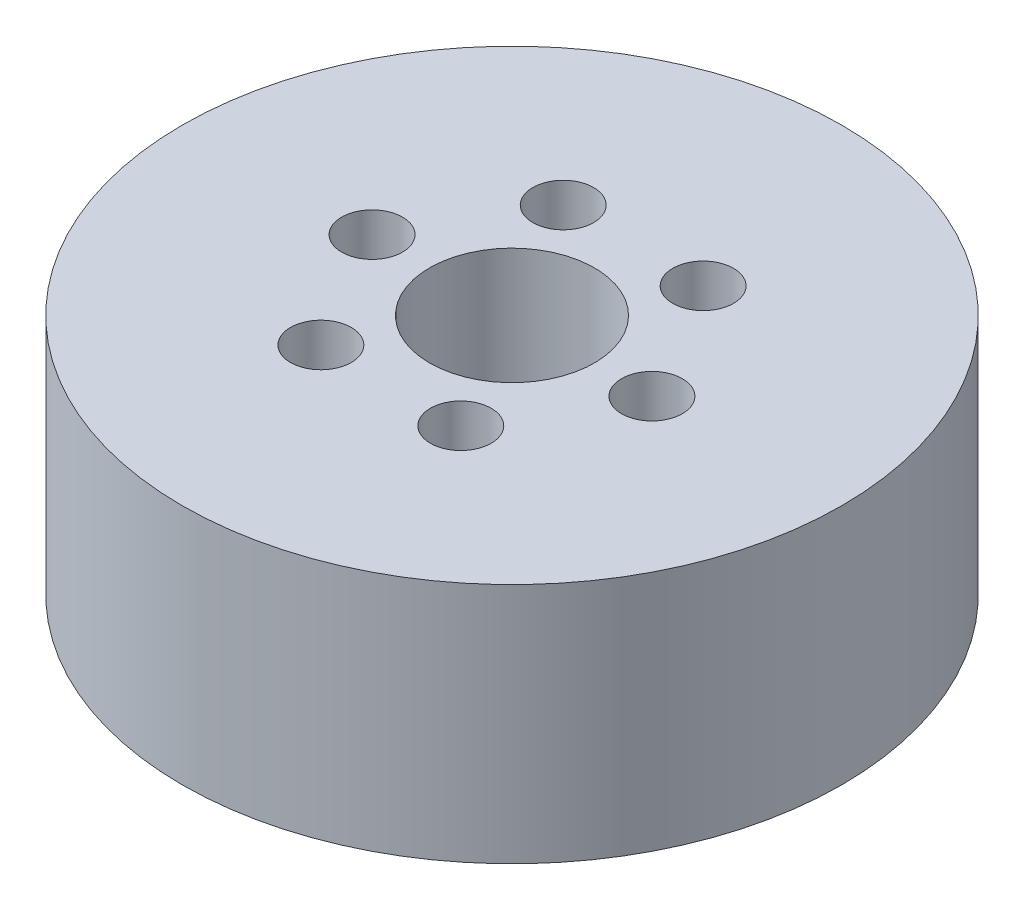
SolidWorks part; units mm, degrees
ref_plane "Front Plane" through (0, 0, 0) normal (0, 0, 1) x (1, 0, 0)
ref_plane "Top Plane" through (0, 0, 0) normal (0, 1, 0) x (1, 0, 0)
ref_plane "Right Plane" through (0, 0, 0) normal (1, 0, 0) x (0, 0, -1)
sketch "Sketch1" plane through (0, 0, 0) normal (0, 1, 0) x (1, 0, 0)
  circle A0 centre (0, 0) radius 30
  dimension "FLANGE_OD" = 60
extrude "Boss-Extrude1" add sketch "Sketch1" along normal blind 22
sketch "Sketch2" plane through (0, 0, 0) normal (0, 1, 0) x (1, 0, 0)
  circle A0 centre (0, 0) radius 7.5
  dimension "BORE_D" = 15
extrude "Cut-Extrude1" cut sketch "Sketch2" along normal through all
sketch "Sketch3" plane through (0, 22, 0) normal (0, 1, 0) x (1, 0, 0)
  circle A0 centre (0, 0) radius 12.7313 construction
  circle A1 centre (-12.7313, 0) radius 2.7657
  dimension "BOLT_D" = 5.5314
  dimension "BOLT_PCD" = 25.4625
extrude "Cut-Extrude2" cut sketch "Sketch3" against normal blind 21.7838
pattern_circular "CirPattern1" count 6 over 360 about axis through (0, 0, 0) along (0, 1, 0) of "Cut-Extrude2"
